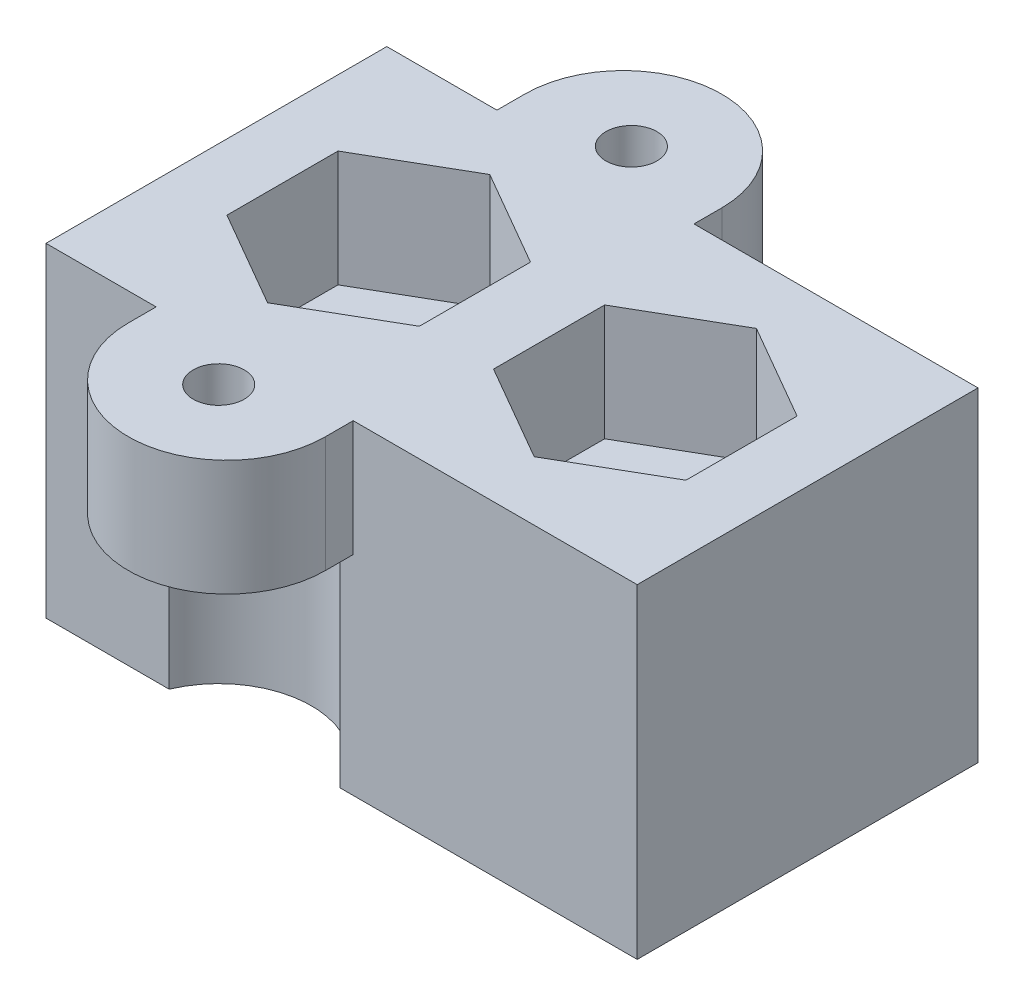
SolidWorks part; units mm, degrees
ref_plane "前视基准面" through (0, 0, 0) normal (0, 0, 1) x (1, 0, 0)
ref_plane "上视基准面" through (0, 0, 0) normal (0, 1, 0) x (1, 0, 0)
ref_plane "右视基准面" through (0, 0, 0) normal (1, 0, 0) x (0, 0, -1)
sketch "草图1" plane through (0, 0, 0) normal (0, 1, 0) x (1, 0, 0)
  line L0 (4.0406, 7.35) -> (4.0406, -7.35) construction
  line L7 (4.0406, -7.35) -> (29.5406, -7.35)
  line L8 (4.0406, -7.35) -> (4.0406, 7.35)
  line L11 (4.0406, 7.35) -> (29.5406, 7.35)
  line L12 (29.5406, -7.35) -> (29.5406, 7.35)
  line L13 (29.5406, -1.4) -> (29.5406, 1.4) construction
  line L14 (17.2906, 7.35) -> (8.7906, 7.35) construction
  line L15 (17.2906, -7.35) -> (8.7906, -7.35) construction
extrude "主体" add sketch "草图1" along normal blind 14
sketch "草图4" plane through (0, 14, 0) normal (0, -1, 0) x (1, 0, 0)
  line L0 (8.7906, -7.35) -> (8.7906, -8.55) construction
  line L1 (8.7906, -7.35) -> (17.2906, -7.35)
  line L2 (8.7906, -7.35) -> (8.7906, -12.8)
  line L3 (8.7906, -12.8) -> (17.2906, -12.8)
  line L4 (17.2906, -7.35) -> (17.2906, -12.8)
  line L6 (11.149, -12.8) -> (22.4321, -12.8) construction
extrude "凸台-拉伸2" add sketch "草图4" along normal blind 5
fillet "圆角1" 2 edges at (8.7906, 11.5, -12.8) (17.2906, 11.5, -12.8) type full round first side face at (8.7906, 11.5, -10.075) second side face at (17.2906, 11.5, -10.075) middle face at (13.0406, 11.5, -12.8)
hole_wizard "M2 间隙孔1" positions "草图5" profile "草图6" hole size "M2" standard "ISO" end condition up to next
sketch "草图5" plane through (0, 9, 0) normal (0, -1, 0) x (-1, 0, 0)
  point P0 (-13.0406, 8.9)
sketch "草图6" plane through (13.0406, 9, -8.9) normal (1, 0, 0) x (0, 0, -1)
  line L0 (0, 0) -> (0, 5)
  line L1 (0, 5) -> (1.1, 5)
  line L2 (1.1, 5) -> (1.1, 0)
  line L5 (1.1, 0) -> (0, 0)
  line L11 (0, -6.35) -> (0, 107.95) construction
  dimension "通孔孔直径" = 2.2
  dimension "通孔孔深度" = 5
sketch "草图7" plane through (0, 0, 0) normal (0, -1, 0) x (1, 0, 0)
  circle A0 centre (13.0406, -8.9) radius 4
extrude "切除-拉伸3" cut sketch "草图7" against normal up to surface (9 mm away) up to face at (13.0406, 9, -10)
mirror "镜向1" about plane through (0, 0, 0) normal (0, 0, 1) of "切除-拉伸3", "M2 间隙孔1", "圆角1", "凸台-拉伸2"
hole_wizard "M5 间隙孔1" positions "草图8" profile "草图9" hole size "M5" standard "ISO" end condition up to next
sketch "草图8" plane through (0, 0, 0) normal (0, -1, 0) x (-1, 0, 0)
  line L0 (-7.7, 0) -> (7.7, 0) construction
  line L1 (-29.5406, -7.35) -> (-29.5406, 7.35) construction
  line L2 (-4.0406, 7.35) -> (-4.0406, -7.35) construction
  point P0 (-22.5406, 0)
  point P2 (-11.0406, 0)
  dimension "D1" = 7
  dimension "D2" = 7
  dimension "D3" = 11.5
sketch "草图9" plane through (22.5406, 0, 0) normal (1, 0, 0) x (0, 0, -1)
  line L0 (0, 0) -> (0, 14)
  line L1 (0, 14) -> (2.65, 14)
  line L2 (2.65, 14) -> (2.65, 0)
  line L5 (2.65, 0) -> (0, 0)
  line L11 (0, -6.35) -> (0, 107.95) construction
  dimension "通孔孔直径" = 5.3
  dimension "通孔孔深度" = 14
sketch "草图10" plane through (0, 14, 0) normal (0, 1, 0) x (1, 0, 0)
  line L1 (11.0406, 4.792) -> (6.8906, 2.396)
  line L2 (6.8906, 2.396) -> (6.8906, -2.396)
  line L3 (6.8906, -2.396) -> (11.0406, -4.792)
  line L4 (11.0406, -4.792) -> (15.1906, -2.396)
  line L5 (15.1906, -2.396) -> (15.1906, 2.396)
  line L6 (15.1906, 2.396) -> (11.0406, 4.792)
  line L7 (22.5406, 4.792) -> (18.3906, 2.396)
  line L8 (18.3906, 2.396) -> (18.3906, -2.396)
  line L9 (18.3906, -2.396) -> (22.5406, -4.792)
  line L10 (22.5406, -4.792) -> (26.6906, -2.396)
  line L11 (26.6906, -2.396) -> (26.6906, 2.396)
  line L12 (26.6906, 2.396) -> (22.5406, 4.792)
  circle A0 centre (11.0406, 0) radius 4.15 construction
  circle A1 centre (22.5406, 0) radius 4.15 construction
  dimension "D1" = 8.3
  dimension "D2" = 8.3
extrude "切除-拉伸4" cut sketch "草图10" against normal blind 5
